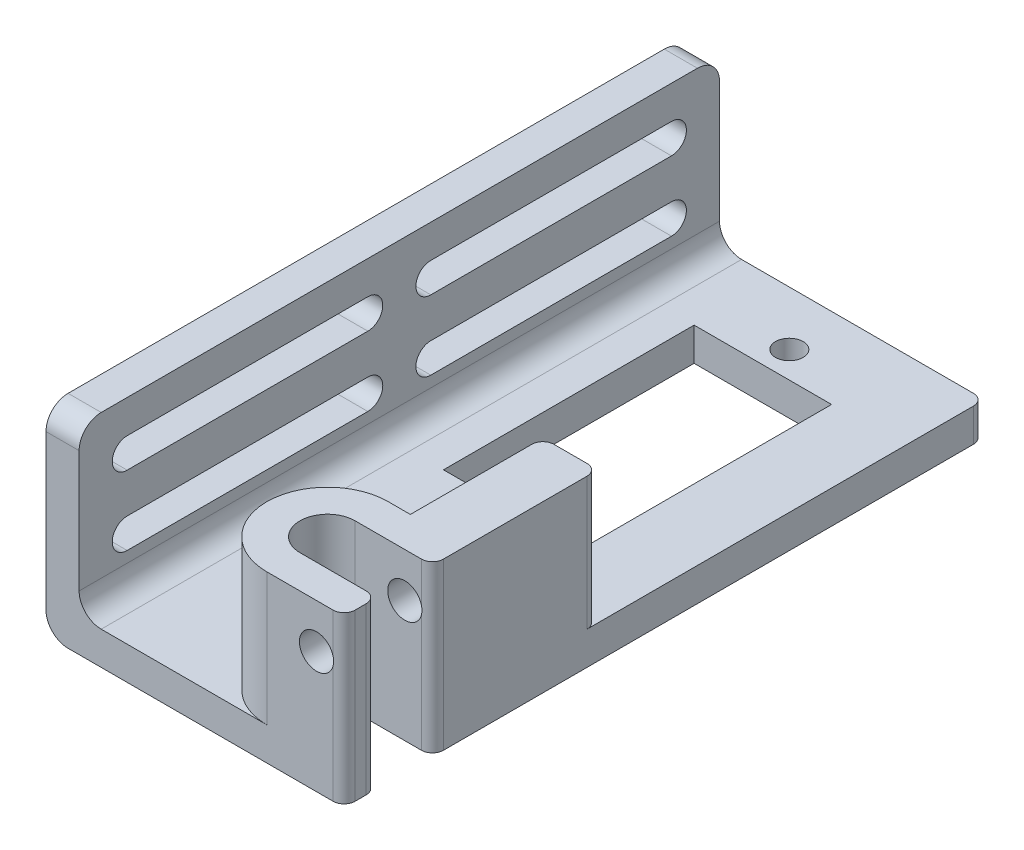
SolidWorks part; units mm, degrees
material "ABS"
ref_plane "Front Plane" through (0, 0, 0) normal (0, 0, 1) x (1, 0, 0)
ref_plane "Top Plane" through (0, 0, 0) normal (0, 1, 0) x (1, 0, 0)
ref_plane "Right Plane" through (0, 0, 0) normal (1, 0, 0) x (0, 0, -1)
sketch "Sketch1" plane through (0, 0, 0) normal (0, 1, 0) x (1, 0, 0)
  line L0 (27, 8) -> (20, 8)
  line L1 (0, 0) -> (27, 0)
  line L2 (0, 0) -> (0, 58)
  line L3 (0, 58) -> (27, 58)
  line L4 (27, 0) -> (27, 3)
  line L5 (27, 3) -> (20, 3)
  line L6 (20, 8) -> (20, 3) construction
  line L7 (27, 8) -> (27, 58)
  arc A0 (20, 3) -> (20, 8) centre (20, 5.5) cw
  dimension "D1" = 58
  dimension "D2" = 27
  dimension "D3" = 5
  dimension "D4" = 3
  dimension "D5" = 7
extrude "Boss-Extrude1" add sketch "Sketch1" along normal blind 3
sketch "Sketch2" plane through (0, 3, 0) normal (0, 1, 0) x (1, 0, 0)
  line L0 (0, 58) -> (0, 0) construction
  line L1 (8, 50.7) -> (20.45, 50.7)
  line L2 (8, 50.7) -> (8, 28)
  line L3 (8, 28) -> (20.45, 28)
  line L4 (20.45, 50.7) -> (20.45, 28)
  line L5 (0, 0) -> (27, 0) construction
  line L6 (14.225, 50.7) -> (14.225, 58) construction
  line L7 (27, 58) -> (0, 58) construction
  circle A1 centre (14.225, 53.1) radius 1.25
  circle A2 centre (14.225, 25.6) radius 1.25
  dimension "D4" = 2.5
  dimension "D5" = 2.5
  dimension "D1" = 12.45
  dimension "D2" = 22.7
  dimension "D3" = 8
  dimension "D6" = 2.4
  dimension "D7" = 2.4
  dimension "D8" = 28
extrude "Cut-Extrude1" cut sketch "Sketch2" against normal blind 3
sketch "Sketch3" plane through (0, 3, 0) normal (0, 1, 0) x (1, 0, 0)
  line L0 (0, 0) -> (27, 0) construction
  line L1 (0, 58) -> (3, 58)
  line L2 (0, 58) -> (0, 0)
  line L3 (0, 0) -> (3, 0)
  line L4 (3, 58) -> (3, 0)
  dimension "D1" = 3
extrude "Boss-Extrude2" add sketch "Sketch3" along normal blind 15
sketch "Sketch4" plane through (0, 3, 0) normal (0, 1, 0) x (1, 0, 0)
  line L0 (3, 0) -> (27, 0) construction
  line L1 (20, 11) -> (22, 11)
  line L2 (27, 8) -> (27, 58) construction
  line L3 (20, 8) -> (27, 8) construction
  line L4 (20, 0) -> (27, 0)
  line L5 (27, 0) -> (27, 3)
  line L6 (27, 3) -> (20, 3)
  line L7 (27, 11) -> (27, 8)
  line L8 (27, 8) -> (20, 8)
  line L11 (27, 11) -> (27, 23)
  line L12 (27, 23) -> (22, 23)
  line L13 (22, 11) -> (22, 23)
  arc A0 (20, 0) -> (20, 11) centre (20, 5.5) cw
  arc A1 (20, 8) -> (20, 3) centre (20, 5.5) ccw construction
  arc A2 (20, 8) -> (20, 3) centre (20, 5.5) ccw
  dimension "D1" = 3
  dimension "D2" = 3
  dimension "D3" = 5
  dimension "D4" = 12
extrude "Boss-Extrude3" add sketch "Sketch4" along normal blind 12
fillet "Fillet1" radius 2 2 edges at (3, 3, -29) (0, 0, -29)
fillet "Fillet2" radius 2 2 edges at (1.5, 18, -58) (1.5, 18, 0)
fillet "Fillet3" radius 1 6 edges at (27, 9, -23) (22, 9, -23) (27, 7.5, -8) (27, 7.5, -3) (27, 7.5, 0) (27, 1.5, -58)
sketch "Sketch5" plane through (0, 0, 0) normal (-1, 0, 0) x (0, 0, 1)
  line L0 (-53.65, 13.65) -> (-31.85, 13.65) construction
  line L1 (-53.65, 15) -> (-31.85, 15)
  line L2 (-53.65, 12.3) -> (-31.85, 12.3)
  line L3 (-53.65, 7.35) -> (-31.85, 7.35) construction
  line L4 (-53.65, 8.7) -> (-31.85, 8.7)
  line L5 (-53.65, 6) -> (-31.85, 6)
  line L6 (-56, 18) -> (-2, 18) construction
  line L7 (-58, 2) -> (0, 2) construction
  line L8 (-26.15, 13.65) -> (-4.35, 13.65) construction
  line L9 (-26.15, 15) -> (-4.35, 15)
  line L10 (-26.15, 12.3) -> (-4.35, 12.3)
  line L11 (-26.15, 7.35) -> (-4.35, 7.35) construction
  line L12 (-26.15, 8.7) -> (-4.35, 8.7)
  line L13 (-26.15, 6) -> (-4.35, 6)
  line L14 (-58, 16) -> (-58, 2) construction
  line L15 (0, 16) -> (0, 2) construction
  line L16 (-29, 18) -> (-29, 2) construction
  arc A0 (-53.65, 15) -> (-53.65, 12.3) centre (-53.65, 13.65) ccw
  arc A1 (-31.85, 12.3) -> (-31.85, 15) centre (-31.85, 13.65) ccw
  arc A2 (-53.65, 8.7) -> (-53.65, 6) centre (-53.65, 7.35) ccw
  arc A3 (-31.85, 6) -> (-31.85, 8.7) centre (-31.85, 7.35) ccw
  arc A4 (-26.15, 15) -> (-26.15, 12.3) centre (-26.15, 13.65) ccw
  arc A5 (-4.35, 12.3) -> (-4.35, 15) centre (-4.35, 13.65) ccw
  arc A6 (-26.15, 8.7) -> (-26.15, 6) centre (-26.15, 7.35) ccw
  arc A7 (-4.35, 6) -> (-4.35, 8.7) centre (-4.35, 7.35) ccw
  point P2 (-42.75, 13.65)
  point P9 (-42.75, 7.35)
  point P20 (-15.25, 13.65)
  point P25 (-15.25, 7.35)
  point P34 (-55, 13.65)
  point P35 (-55, 7.35)
  point P36 (-3, 13.65)
  point P39 (-3, 7.35)
  point P40 (-30.5, 13.65)
  point P41 (-30.5, 7.35)
  point P42 (-27.5, 13.65)
  point P43 (-27.5, 7.35)
  dimension "D8" = 3
  dimension "D1" = 2.7
  dimension "D2" = 2.7
  dimension "D3" = 3
  dimension "D4" = 4
  dimension "D5" = 2.7
  dimension "D6" = 2.7
  dimension "D7" = 3
  dimension "D9" = 3
  dimension "D10" = 3
  dimension "D11" = 1.5
  dimension "D12" = 1.5
  dimension "D13" = 1.5
  dimension "D14" = 1.5
  dimension "D15" = 6.3
extrude "Cut-Extrude2" cut sketch "Sketch5" against normal blind 3
sketch "Sketch7" plane through (0, 0, -23) normal (0, 0, -1) x (-1, 0, 0)
  line L0 (-24.5, 15) -> (-24.5, 3) construction
  line L1 (-26, 15) -> (-23, 15) construction
  line L2 (-26, 3) -> (-23, 3) construction
  circle A0 centre (-24.5, 11) radius 1.55
  dimension "D1" = 3.1
  dimension "D2" = 4
extrude "Cut-Extrude3" cut sketch "Sketch7" against normal through all
